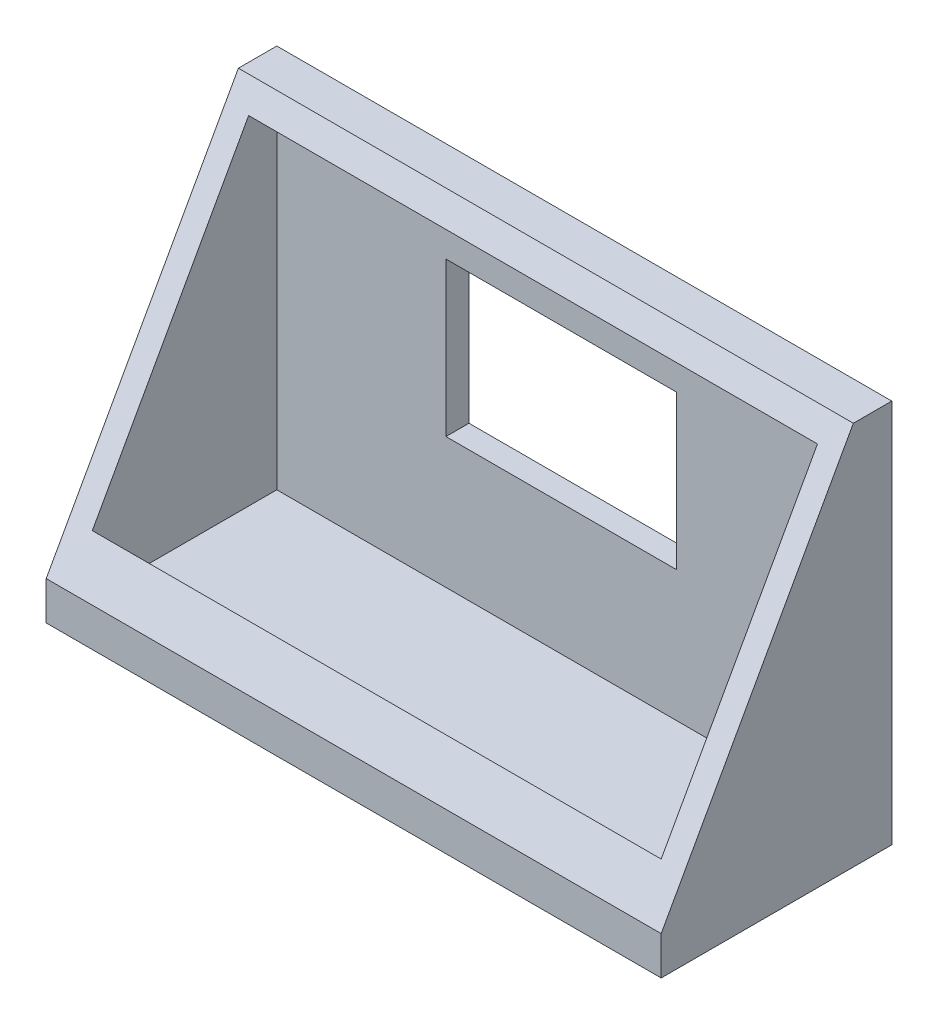
SolidWorks part; units mm, degrees
ref_plane "Přední rovina" through (0, 0, 0) normal (0, 0, 1) x (1, 0, 0)
ref_plane "Vrchní rovina" through (0, 0, 0) normal (0, 1, 0) x (1, 0, 0)
ref_plane "Pravá rovina" through (0, 0, 0) normal (1, 0, 0) x (0, 0, -1)
sketch "Skica1" plane through (0, 0, 0) normal (1, 0, 0) x (0, 0, -1)
  line L0 (-30, 0) -> (0, 0)
  line L1 (0, 0) -> (0, 50)
  line L2 (0, 50) -> (-5, 50)
  line L3 (-5, 50) -> (-30, 5)
  line L4 (-30, 5) -> (-30, 0)
  dimension "D1" = 30
  dimension "D2" = 50
  dimension "D3" = 5
  dimension "D4" = 5
extrude "Přidat vysunutím1" add sketch "Skica1" along normal mid plane 80
shell "Skořepina1" thickness 3 removed face at (0, 27.5, 17.5)
sketch "Skica2" plane through (0, 0, 0) normal (0, 0, -1) x (-1, 0, 0)
  line L0 (0, 30) -> (0, 0) construction
  line L1 (15, 20) -> (-15, 20)
  line L2 (15, 20) -> (15, 40)
  line L3 (15, 40) -> (-15, 40)
  line L4 (-15, 20) -> (-15, 40)
  line L5 (15, 20) -> (-15, 40) construction
  line L6 (15, 40) -> (-15, 20) construction
  line L7 (-40, 0) -> (40, 0) construction
  line L8 (-40, 50) -> (40, 50) construction
  line L9 (-30, 30) -> (0, 30) construction
  line L10 (-30, 30) -> (-40, 30) construction
  line L11 (-40, 0) -> (-40, 50) construction
  circle A0 centre (-30, 30) radius 5
  circle A2 centre (-30, 30) radius 4
  point P0 (0, 30)
  point P14 (0, 0)
  dimension "D4" = 10
  dimension "D5" = 8
  dimension "D1" = 30
  dimension "D2" = 20
  dimension "D3" = 10
  dimension "D6" = 10
extrude "Odebrat vysunutím1" cut sketch "Skica2" against normal blind 80 contours L2 L1 L4 L3
extrude "Přidat vysunutím2" add sketch "Skica2<3>" along normal blind 5 contours A2 | A0 region at (30, 30, 0)
sketch "Skica2<3>" plane through (0, 0, 0) normal (0, 0, -1) x (-1, 0, 0) same geometry as "Skica2"
mirror "Zrcadlit1" about plane through (0, 0, 0) normal (1, 0, 0) of "Přidat vysunutím2"
